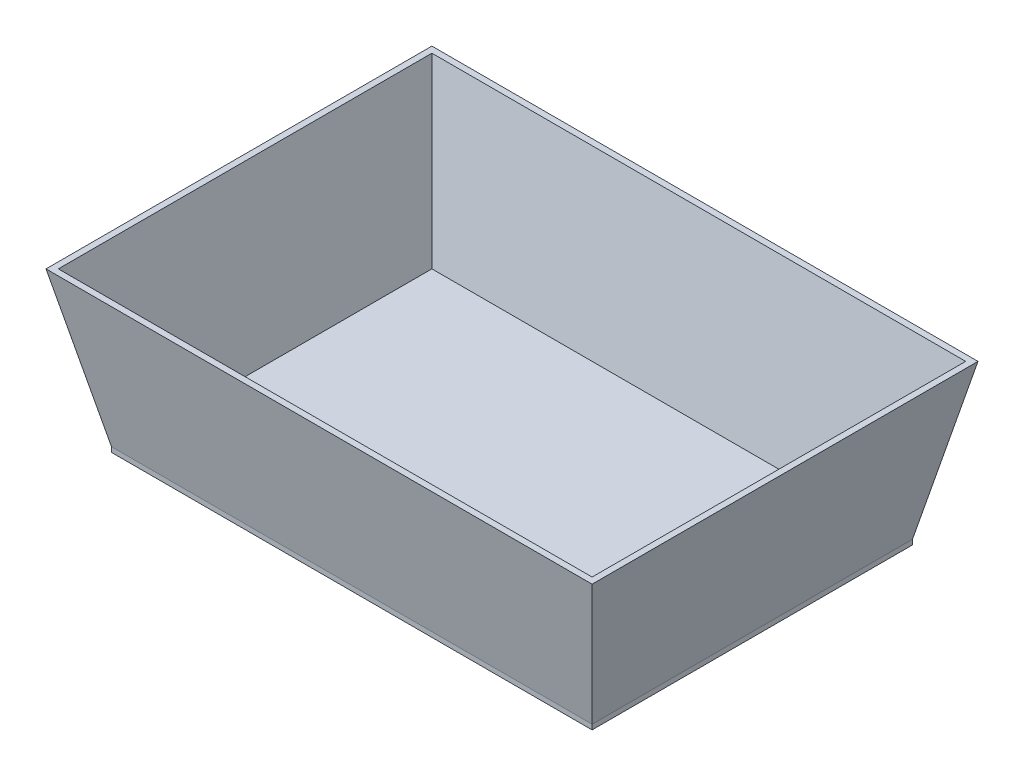
SolidWorks part; units mm, degrees
ref_plane "Front Plane" through (0, 0, 0) normal (0, 0, 1) x (1, 0, 0)
ref_plane "Top Plane" through (0, 0, 0) normal (0, 1, 0) x (1, 0, 0)
ref_plane "Right Plane" through (0, 0, 0) normal (1, 0, 0) x (0, 0, -1)
sketch "Sketch2" plane through (0, 0, 0) normal (0, 1, 0) x (1, 0, 0)
  line L1 (-123.825, -82.55) -> (123.825, -82.55)
  line L2 (-123.825, -82.55) -> (-123.825, 82.55)
  line L3 (-123.825, 82.55) -> (123.825, 82.55)
  line L4 (123.825, -82.55) -> (123.825, 82.55)
  line L5 (-123.825, -82.55) -> (123.825, 82.55) construction
  line L6 (-123.825, 82.55) -> (123.825, -82.55) construction
  point P0 (0, 0)
  dimension "D1" = 247.65
  dimension "D2" = 165.1
extrude "Boss-Extrude2" add sketch "Sketch2" along normal blind 79.375 draft 12 draft outward yes
sketch "Sketch3" plane through (0, 79.375, 0) normal (0, 1, 0) x (1, 0, 0)
  line L0 (140.6967, 99.4217) -> (-140.6967, 99.4217) construction
  line L1 (-137.5217, -96.2467) -> (137.5217, -96.2467)
  line L2 (-137.5217, -96.2467) -> (-137.5217, 96.2467)
  line L3 (-137.5217, 96.2467) -> (137.5217, 96.2467)
  line L4 (137.5217, -96.2467) -> (137.5217, 96.2467)
  line L5 (-137.5217, -96.2467) -> (137.5217, 96.2467) construction
  line L6 (-137.5217, 96.2467) -> (137.5217, -96.2467) construction
  line L7 (-140.6967, 99.4217) -> (-140.6967, -99.4217) construction
  point P0 (0, 0)
  dimension "D1" = 3.175
  dimension "D2" = 3.175
extrude "Cut-Extrude1" cut sketch "Sketch3" against normal blind 139.7 draft 12
sketch "Sketch4" plane through (0, 0, 0) normal (0, -1, 0) x (1, 0, 0)
  line L1 (123.825, -82.55) -> (-123.825, -82.55)
  line L2 (123.825, -82.55) -> (123.825, 82.55)
  line L3 (123.825, 82.55) -> (-123.825, 82.55)
  line L4 (-123.825, -82.55) -> (-123.825, 82.55)
  line L5 (123.825, -82.55) -> (-123.825, 82.55) construction
  line L6 (123.825, 82.55) -> (-123.825, -82.55) construction
  point P1 (0, 0)
extrude "Boss-Extrude3" add sketch "Sketch4" along normal blind 2.54
